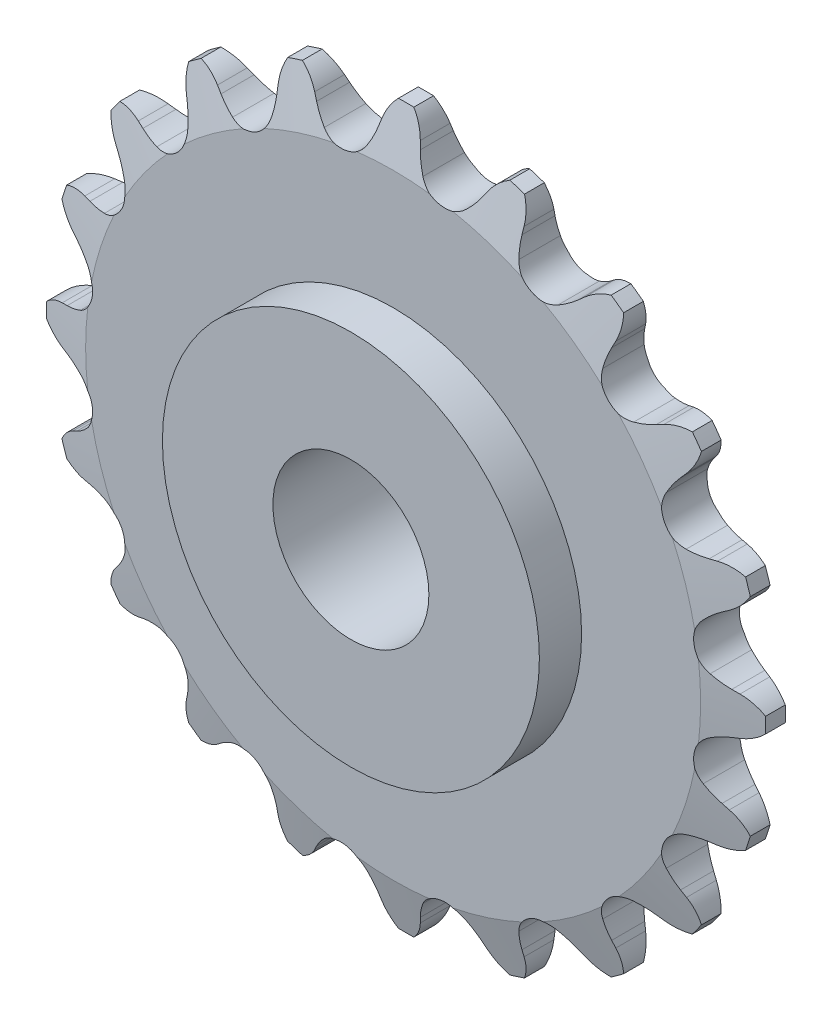
SolidWorks part; units mm, degrees
ref_plane "Front Plane" through (0, 0, 0) normal (0, 0, 1) x (1, 0, 0)
ref_plane "Top Plane" through (0, 0, 0) normal (0, 1, 0) x (1, 0, 0)
ref_plane "Right Plane" through (0, 0, 0) normal (1, 0, 0) x (0, 0, -1)
sketch "Sketch0" plane through (0, 0, 0) normal (0, 0, 1) x (1, 0, 0)
  line L0 (3.175, -20.0462) -> (0, 0) construction
  line L1 (0, 0) -> (9.2142, -18.0839) construction
  line L2 (0, 0) -> (-3.175, -20.0462) construction
  line L3 (3.175, -20.0462) -> (9.2142, -18.0839) construction
  line L4 (3.175, -20.0462) -> (-3.175, -20.0462) construction
  line L5 (5.2772, -20.0402) -> (5.0611, -19.6917)
  line L6 (3.175, -20.0462) -> (0, -20.549) construction
  line L7 (1.1739, -20.6901) -> (1.2717, -20.2918)
  line L8 (0, -20.0462) -> (0, -21.9512) construction
  line L9 (4.3326, -18.8048) -> (1.3734, -21.9781) construction
  line L10 (0, 0) -> (0, -20.0462) construction
  line L11 (5.0611, -19.6917) -> (1.3734, -21.9781) construction
  line L12 (0, -21.9512) -> (0, -22.3247) construction
  line L13 (7.5715, -18.6176) -> (5.2772, -20.0402) construction
  circle A0 centre (0, 0) radius 21.9512 construction
  circle A1 centre (0, 0) radius 20.296 construction
  arc A2 (-1.6423, -22.7387) -> (8.5885, -21.1183) centre (0, 0) ccw
  circle A3 centre (0, 0) radius 22.3247 construction
  circle A4 centre (3.175, -20.0462) radius 1.651 construction
  arc A7 (4.3326, -18.8048) -> (1.6905, -19.2233) centre (3.175, -20.0462) ccw
  circle A8 centre (3.175, -20.0462) radius 1.6974 construction
  arc A9 (5.2772, -20.0402) -> (8.5885, -21.1183) centre (7.5715, -18.6176) ccw
  arc A10 (5.0611, -19.6917) -> (4.3326, -18.8048) centre (1.3734, -21.9781) ccw
  arc A11 (1.1739, -20.6901) -> (-1.6423, -22.7387) centre (-1.4478, -20.0462) cw
  arc A12 (1.2717, -20.2918) -> (1.6905, -19.2233) centre (5.4854, -21.3268) cw
  dimension "D1" = 1.6974
  dimension "R" = 1.6974
sketch "Sketch1" plane through (0, 0, 0) normal (1, 0, 0) x (0, 0, -1)
  line L0 (-1.397, 0) -> (1.397, 0)
  line L1 (-1.397, 0) -> (-1.397, 18.7762)
  line L2 (-1.397, 18.7762) -> (-0.6032, 21.9512)
  line L3 (-0.6032, 21.9512) -> (0.6032, 21.9512)
  line L4 (0.6032, 21.9512) -> (1.397, 18.7762)
  line L5 (1.397, 18.7762) -> (1.397, 0)
  line L7 (0, 21.9512) -> (0, 0) construction
  line L8 (-1.397, 18.7762) -> (1.397, 18.7762) construction
  line L9 (0, 21.9512) -> (0, -21.9512) construction
  line L10 (-1.397, 18.7762) -> (-1.397, 21.9512) construction
  line L11 (-1.397, 21.9512) -> (-0.6032, 21.9512) construction
  line L12 (0.6032, 21.9512) -> (1.397, 21.9512) construction
  line L13 (1.397, 21.9512) -> (1.397, 18.7762) construction
revolve "Revolve1" add sketch "Sketch1" angle 360 mid plane about L0
extrude "Cut-Extrude1" cut sketch "Sketch0" against normal through all and the other way through all
pattern_circular "CirPattern1" count 20 over 360 about axis through (0, 0, 1.397) along (0, 0, 1) of "Cut-Extrude1"
sketch "Sketch2" plane through (0, 0, 0) normal (0, 0, 1) x (1, 0, 0)
  circle A0 centre (0, 0) radius 4.7625 construction
  circle A1 centre (0, 0) radius 11.5094
  circle A2 centre (0, 0) radius 21.971 construction
  dimension "Bore" = 9.525
  dimension "Hub Dia." = 23.0188
  dimension "OD" = 43.942
extrude "Boss-Extrude1" add sketch "Sketch2" along normal mid plane 7.9502
sketch "Sketch3" plane through (0, 0, 0) normal (0, 0, 1) x (1, 0, 0)
  circle A0 centre (0, 0) radius 4.7625 construction
  circle A1 centre (0, 0) radius 4.7625
extrude "Cut-Extrude2" cut sketch "Sketch3" along normal through all and the other way through all
equation "\"360/N@Sketch0\" = 360/\"Teeth@CirPattern1\""
equation "\"Ds@Sketch0\" = 1.005 * \"Dr@Sketch0\" + 0.003"
equation "\"R@Sketch0\" = 1/2 * \"Ds@Sketch0\""
equation "\"A@Sketch0\" = 35 +  ( 60 / \"Teeth@CirPattern1\" ) "
equation "\"B@Sketch0\" = 18 -  ( 56 / \"Teeth@CirPattern1\" )"
equation "\"ac@Sketch0\" = 0.8 * \"Dr@Sketch0\""
equation "\"ab@Sketch0\" = 1.4 * \"Dr@Sketch0\""
equation "\"J@Sketch0\" = 0.3 * \"Pitch@Sketch0\""
equation "\"h@Sketch1\" = \"Pitch@Sketch0\" / 2"
equation "\"g@Sketch1\" = \"h@Sketch1\" / 4"
